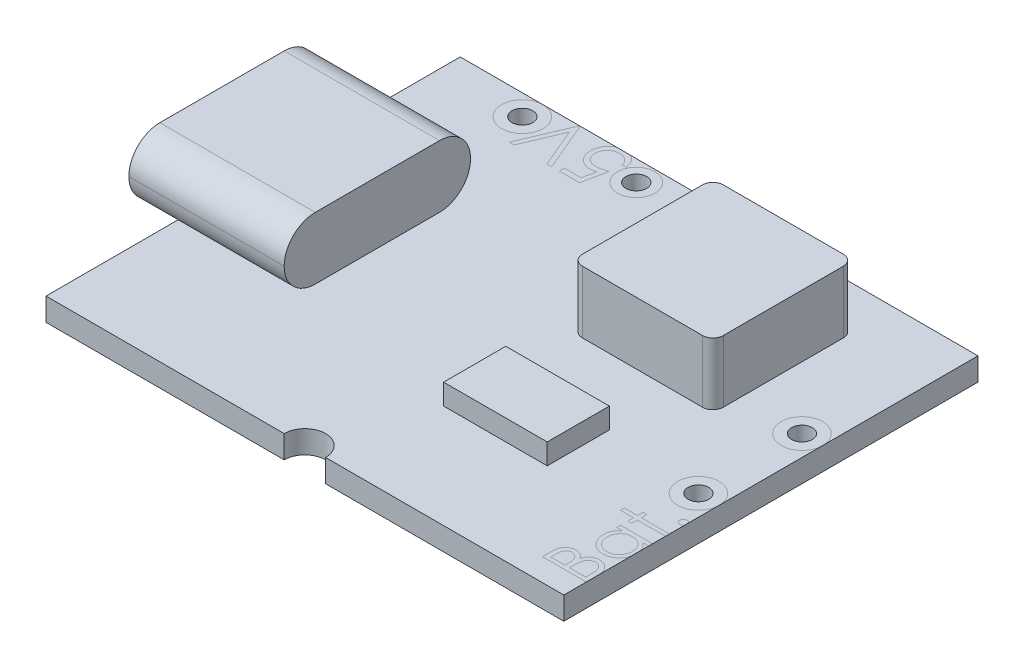
SolidWorks part; units mm, degrees
ref_plane "Alzado" through (0, 0, 0) normal (0, 0, 1) x (1, 0, 0)
ref_plane "Planta" through (0, 0, 0) normal (0, 1, 0) x (1, 0, 0)
ref_plane "Vista lateral" through (0, 0, 0) normal (1, 0, 0) x (0, 0, -1)
sketch "Croquis1" plane through (0, 0, 0) normal (0, 1, 0) x (1, 0, 0)
  line L0 (-12.5, 0) -> (12.5, 0) construction
  line L1 (-12.5, 10) -> (-1, 10)
  line L2 (-12.5, 10) -> (-12.5, -10)
  line L3 (-12.5, -10) -> (-1, -10)
  line L4 (12.5, 10) -> (12.5, -10)
  line L5 (-12.5, 10) -> (12.5, -10) construction
  line L6 (-12.5, -10) -> (12.5, 10) construction
  line L7 (0, 9) -> (0, -9) construction
  line L8 (1, 10) -> (12.5, 10)
  line L9 (1, -10) -> (12.5, -10)
  arc A0 (-1, 10) -> (1, 10) centre (0, 10) ccw
  arc A1 (-1, -10) -> (1, -10) centre (0, -10) cw
  circle A2 centre (11.5, 2.5) radius 0.5
  circle A3 centre (11.5, -2.5) radius 0.5
  circle A4 centre (-8.5, 9) radius 0.5
  circle A5 centre (-3, 9) radius 0.5
  point P0 (0, 0)
  dimension "D3" = 2
  dimension "D5" = 1
  dimension "D8" = 1
  dimension "D1" = 25
  dimension "D2" = 20
  dimension "D4" = 12.5
  dimension "D6" = 5
  dimension "D7" = 1
  dimension "D9" = 4
  dimension "D10" = 5.5
  dimension "D11" = 1
extrude "Saliente-Extruir1" add sketch "Croquis1" along normal blind 1.1
sketch "Croquis2" plane through (0, 1.1, 0) normal (0, 1, 0) x (1, 0, 0)
  line L0 (-12.5, 10) -> (-12.5, -10) construction
  line L1 (-14, 4.5) -> (-6.5, 4.5)
  line L2 (-14, 4.5) -> (-14, -4.5)
  line L3 (-14, -4.5) -> (-6.5, -4.5)
  line L4 (-6.5, 4.5) -> (-6.5, -4.5)
  point P4 (-14, 0)
  dimension "D1" = 7.5
  dimension "D2" = 9
  dimension "D3" = 6
extrude "Saliente-Extruir2" add sketch "Croquis2" along normal blind 3 separate body
fillet "Redondeo1" radius 1.5 4 edges at (-10.25, 1.1, -4.5) (-10.25, 4.1, -4.5) (-10.25, 1.1, 4.5) (-10.25, 4.1, 4.5)
combine bodies "Combinar1" operation type add bodies to combine 102 101
sketch "Croquis3" plane through (0, 1.1, 0) normal (0, 1, 0) x (1, 0, 0)
  line L0 (12.5, -10) -> (12.5, 10) construction
  line L1 (1.7, 8) -> (8.5, 8)
  line L2 (1.7, 8) -> (1.7, 1.2)
  line L3 (1.7, 1.2) -> (8.5, 1.2)
  line L4 (8.5, 8) -> (8.5, 1.2)
  line L5 (1.7, 8) -> (8.5, 1.2) construction
  line L6 (1.7, 1.2) -> (8.5, 8) construction
  line L7 (12.5, 10) -> (1, 10) construction
  point P0 (5.1, 4.6)
  dimension "D1" = 6.8
  dimension "D2" = 4
  dimension "D3" = 2
extrude "Saliente-Extruir3" add sketch "Croquis3" along normal blind 3
fillet "Redondeo2" radius 0.5 4 edges at (1.7, 2.6, -1.2) (1.7, 2.6, -8) (8.5, 2.6, -8) (8.5, 2.6, -1.2)
sketch "Croquis4" plane through (0, 1.1, 0) normal (0, 1, 0) x (1, 0, 0)
  line L0 (1, -10) -> (12.5, -10) construction
  line L1 (1.7, -2) -> (6.7, -2)
  line L2 (1.7, -2) -> (1.7, -5)
  line L3 (1.7, -5) -> (6.7, -5)
  line L4 (6.7, -2) -> (6.7, -5)
  dimension "D1" = 5
  dimension "D2" = 3
  dimension "D3" = 5
extrude "Saliente-Extruir4" add sketch "Croquis4" along normal blind 1
sketch "Croquis5" plane through (0, 1.1, 0) normal (0, 1, 0) x (1, 0, 0)
  circle A7 centre (-8.5, 9) radius 1
  circle A8 centre (-8.5, 9) radius 1
  circle A10 centre (-3, 9) radius 0.9
  circle A11 centre (-3, 9) radius 0.9
  circle A16 centre (11.5, -2.5) radius 1
  circle A17 centre (11.5, -2.5) radius 1
  circle A19 centre (11.5, 2.5) radius 1
  circle A20 centre (11.5, 2.5) radius 1
  text T0 "   5V" font "Century Gothic" height in points 9
  text T1 " Bat." font "Century Gothic" height in points 8
  dimension "D1" = 0.5
  dimension "D2" = 0.4
  dimension "D3" = 0.5
  dimension "D4" = 0.5
split line "Línea de partición1"
